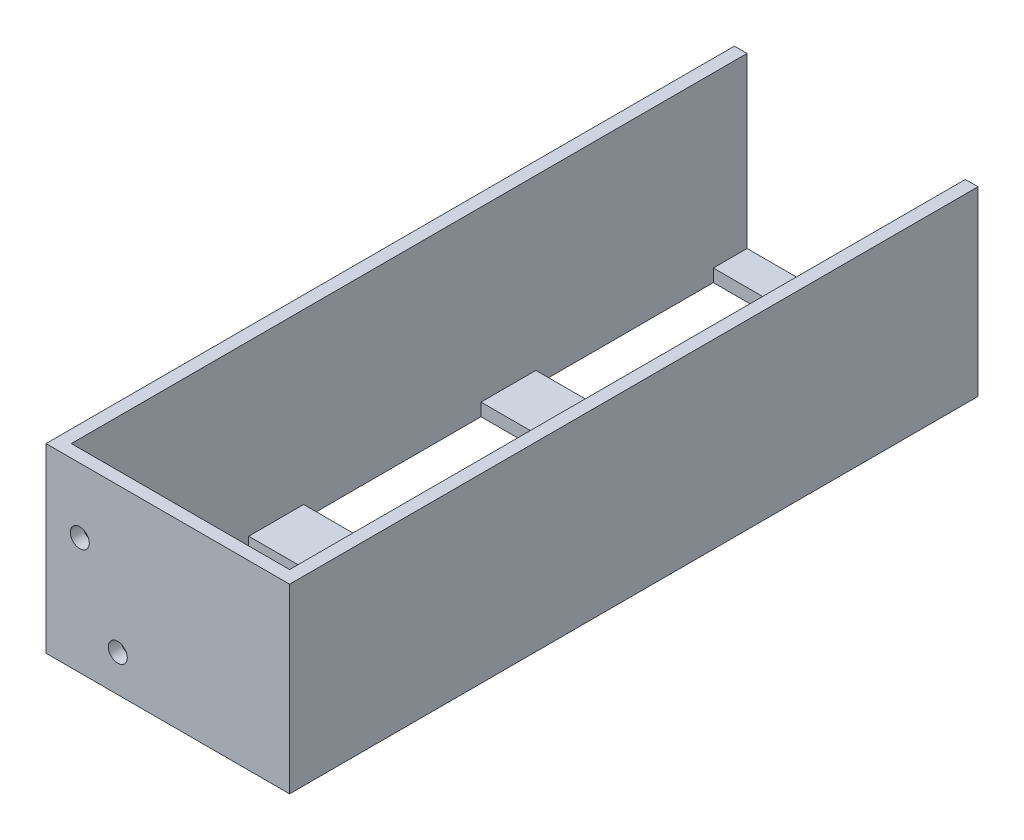
SolidWorks part; units mm, degrees
ref_plane "Front Plane" through (0, 0, 0) normal (0, 0, 1) x (1, 0, 0)
ref_plane "Top Plane" through (0, 0, 0) normal (0, 1, 0) x (1, 0, 0)
ref_plane "Right Plane" through (0, 0, 0) normal (1, 0, 0) x (0, 0, -1)
sketch "Sketch1" plane through (0, 0, 0) normal (0, 0, 1) x (1, 0, 0)
  line L0 (0, 0) -> (0, -10)
  line L1 (0, -10) -> (0, -40)
  line L2 (0, -40) -> (51.6786, -40)
  line L5 (-3, 0) -> (-3, -10)
  line L6 (-3, -10) -> (-3, -43)
  line L7 (-3, -43) -> (54.6786, -43)
  line L10 (-3, 0) -> (0, 0)
  line L12 (51.6786, -40) -> (51.6786, 0)
  line L13 (51.6786, -40) -> (51.6786, 37.6119) construction
  line L14 (51.6786, 37.6119) -> (67.0297, -2.1736) construction
  line L15 (54.6786, -43) -> (54.6786, 21.503) construction
  line L16 (54.6786, 21.503) -> (64.2308, -3.2535) construction
  line L17 (51.6786, 0) -> (54.6786, 0)
  line L18 (54.6786, 0) -> (54.6786, -43)
  dimension "D2" = 10
  dimension "D3" = 30
  dimension "D5" = 3
  dimension "D1" = 3
extrude "Boss-Extrude1" add sketch "Sketch1" along normal blind 160
sketch "Sketch2" plane through (0, 0, 0) normal (0, 1, 0) x (1, 0, 0)
  line L0 (51.6786, -160) -> (0, -160) construction
  line L1 (45, -8) -> (0, -8)
  line L2 (45, -8) -> (45, -50)
  line L3 (45, -50) -> (0, -50)
  line L4 (0, -8) -> (0, -50)
  line L5 (45, -63) -> (0, -63)
  line L6 (45, -63) -> (45, -105)
  line L7 (45, -105) -> (0, -105)
  line L8 (0, -63) -> (0, -105)
  line L9 (45, -118) -> (0, -118)
  line L10 (45, -118) -> (45, -160)
  line L11 (45, -160) -> (0, -160)
  line L12 (0, -118) -> (0, -160)
  line L13 (0, -160) -> (0, 0) construction
  dimension "D1" = 42
  dimension "D2" = 13
  dimension "D3" = 42
  dimension "D4" = 13
  dimension "D5" = 42
  dimension "D6" = 45
extrude "Cut-Extrude1" cut sketch "Sketch2" against normal through all
sketch "Sketch3" plane through (0, 0, 160) normal (0, 0, 1) x (1, 0, 0)
  line L0 (-3, 0) -> (54.6786, 0)
  line L1 (54.6786, 0) -> (54.6786, -43)
  line L2 (54.6786, -43) -> (0, -43)
  line L10 (0, 0) -> (-3, 0)
  line L11 (-3, 0) -> (-3, -43)
  line L13 (-3, -43) -> (0, -43)
  line L18 (0, -43) -> (0, 0)
  line L21 (-3, 0) -> (-3, -43)
  line L23 (-3, -43) -> (0, -43)
  dimension "D1" = 0
extrude "Boss-Extrude2" add sketch "Sketch3" along normal blind 3
sketch "Sketch4" plane through (0, 0, 163) normal (0, 0, 1) x (1, 0, 0)
  circle A0 centre (14, -34.2995) radius 2.25 construction
  circle A1 centre (5, -15.3106) radius 2.25 construction
  circle A2 centre (14, -34.2995) radius 2.25
  circle A3 centre (5, -15.3106) radius 2.25
extrude "Cut-Extrude2" cut sketch "Sketch4" against normal up to next
